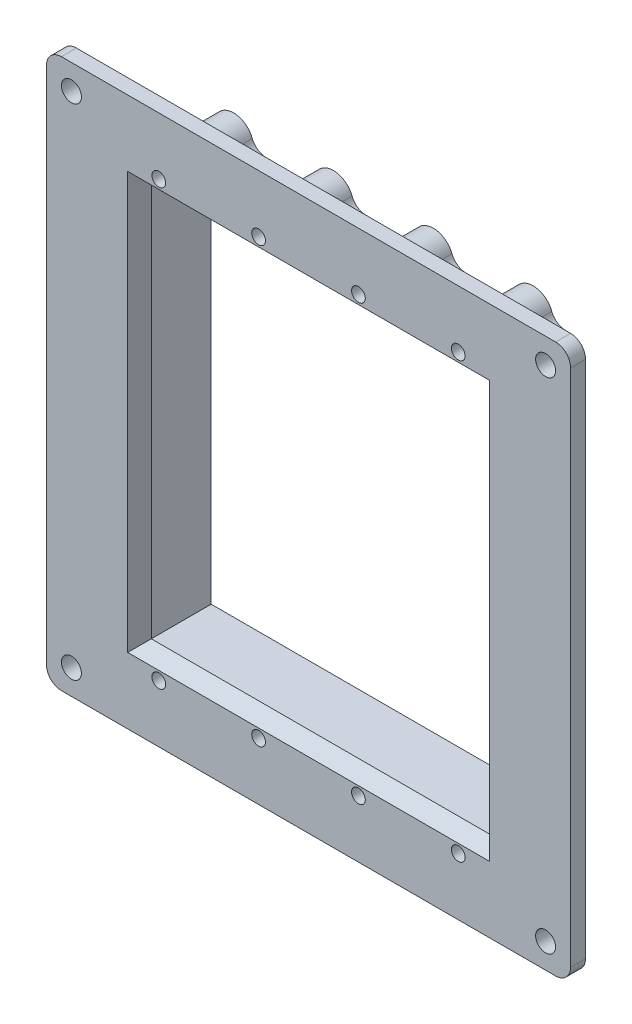
SolidWorks part; units mm, degrees
ref_plane "Front Plane" through (0, 0, 0) normal (0, 0, 1) x (1, 0, 0)
ref_plane "Top Plane" through (0, 0, 0) normal (0, 1, 0) x (1, 0, 0)
ref_plane "Right Plane" through (0, 0, 0) normal (1, 0, 0) x (0, 0, -1)
sketch "Sketch1" plane through (0, 0, 0) normal (0, 0, 1) x (1, 0, 0)
  line L0 (0, 43) -> (0, 43.5) construction
  line L1 (-52.5, 55) -> (52.5, 55)
  line L2 (-52.5, 55) -> (-52.5, -55)
  line L3 (-52.5, -55) -> (52.5, -55)
  line L4 (52.5, 55) -> (52.5, -55)
  line L5 (-52.5, 55) -> (52.5, -55) construction
  line L6 (-52.5, -55) -> (52.5, 55) construction
  line L7 (-37.5, 43) -> (37.5, 43)
  line L8 (-37.5, 43) -> (-37.5, -43)
  line L9 (-37.5, -43) -> (37.5, -43)
  line L10 (37.5, 43) -> (37.5, -43)
  line L11 (-37.5, 43) -> (37.5, -43) construction
  line L12 (-37.5, -43) -> (37.5, 43) construction
  line L13 (-34.5, 40) -> (34.5, 40)
  line L14 (-34.5, 40) -> (-34.5, -40)
  line L15 (-34.5, -40) -> (34.5, -40)
  line L16 (34.5, 40) -> (34.5, -40)
  line L17 (-34.5, 40) -> (34.5, -40) construction
  line L18 (-34.5, -40) -> (34.5, 40) construction
  line L19 (-47.5, -50) -> (47.5, -50) construction
  line L20 (-47.5, -50) -> (-47.5, 50) construction
  line L21 (-47.5, 50) -> (47.5, 50) construction
  line L22 (47.5, -50) -> (47.5, 50) construction
  line L23 (-47.5, -50) -> (47.5, 50) construction
  line L24 (-47.5, 50) -> (47.5, -50) construction
  line L25 (0, 43.5) -> (37.5, 43.5) construction
  line L26 (37.5, 43.5) -> (37.5, 43) construction
  line L27 (30, 43.5) -> (30, 43) construction
  line L28 (34, 43.5) -> (34, 43)
  line L29 (26, 43.5) -> (26, 43)
  line L30 (14, 43.5) -> (14, 43)
  line L31 (6, 43.5) -> (6, 43)
  line L32 (0, 0) -> (0, 55) construction
  line L33 (0, 0) -> (-52.5, 0) construction
  line L34 (-34, 43.5) -> (-34, 43)
  line L35 (-26, 43.5) -> (-26, 43)
  line L36 (-6, 43.5) -> (-6, 43)
  line L37 (-14, 43.5) -> (-14, 43)
  line L38 (30, -43.5) -> (30, -43) construction
  line L39 (37.5, -43.5) -> (37.5, -43) construction
  line L41 (0, -43) -> (0, -43.5) construction
  line L42 (-14, -43.5) -> (-14, -43)
  line L43 (-6, -43.5) -> (-6, -43)
  line L44 (-26, -43.5) -> (-26, -43)
  line L45 (-34, -43.5) -> (-34, -43)
  line L46 (6, -43.5) -> (6, -43)
  line L47 (14, -43.5) -> (14, -43)
  line L48 (26, -43.5) -> (26, -43)
  line L49 (34, -43.5) -> (34, -43)
  circle A0 centre (-47.5, 50) radius 2
  circle A1 centre (47.5, 50) radius 2
  circle A2 centre (-47.5, -50) radius 2
  circle A3 centre (47.5, -50) radius 2
  circle A5 centre (30, 43.5) radius 1.375
  circle A6 centre (10, 43.5) radius 1.375
  arc A7 (34, 43.5) -> (26, 43.5) centre (30, 43.5) ccw
  arc A9 (14, 43.5) -> (6, 43.5) centre (10, 43.5) ccw
  arc A10 (-34, 43.5) -> (-26, 43.5) centre (-30, 43.5) cw
  circle A11 centre (-30, 43.5) radius 1.375
  circle A12 centre (-10, 43.5) radius 1.375
  arc A13 (-14, 43.5) -> (-6, 43.5) centre (-10, 43.5) cw
  arc A14 (-14, -43.5) -> (-6, -43.5) centre (-10, -43.5) ccw
  circle A15 centre (-10, -43.5) radius 1.375
  circle A16 centre (-30, -43.5) radius 1.375
  arc A17 (-34, -43.5) -> (-26, -43.5) centre (-30, -43.5) ccw
  arc A18 (14, -43.5) -> (6, -43.5) centre (10, -43.5) cw
  arc A19 (34, -43.5) -> (26, -43.5) centre (30, -43.5) cw
  circle A20 centre (10, -43.5) radius 1.375
  circle A21 centre (30, -43.5) radius 1.375
  point P0 (0, 0)
  point P6 (0, 0)
  point P11 (0, 0)
  point P16 (0, 0)
  point P33 (50, 19.5)
  point P86 (50, -19.5)
  dimension "D7" = 4
  dimension "D13" = 2.75
  dimension "D14" = 4
  dimension "D1" = 3
  dimension "D2" = 105
  dimension "D3" = 75
  dimension "D4" = 3
  dimension "D5" = 80
  dimension "D6" = 110
  dimension "D8" = 5
  dimension "D9" = 5
  dimension "D10" = 0.5
  dimension "D11" = 10
  dimension "D12" = 20
  dimension "D15" = 2
extrude "Boss-Extrude1" add sketch "Sketch1" along normal blind 3 contours L4 L1 L2 L3 A3 A2 A1 A0 L49 A19 L48 L9 L47 A18 L46 L43 A14 L42 L44 A17 L45 L8 L7 L34 A10 L35 L37 A13 L36 L31 A9 L30 L29 A7 L28 L10 | L10 L7 L8 L9 L13 L16 L15 L14 | L28 A7 L29 L7 A5 | L30 A9 L31 L7 A6 | A13 L37 L7 L36 A12 | A10 L34 L7 L35 A11 | L45 A17 L44 L9 A16 | L42 A14 L43 L9 A15 | A18 L47 L9 L46 A20 | A19 L49 L9 L48 A21 region at (0, 53.4793, 0) region at (-35.75, 41.8589, 0) region at (-30, 45.1224, 0) region at (-30, -45.1224, 0) region at (-10, 45.1224, 0) region at (-10, -45.1224, 0) region at (10, 45.1224, 0) region at (10, -45.1224, 0) region at (30, 45.1224, 0) region at (30, -45.1224, 0)
extrude "Boss-Extrude2" add sketch "Sketch1<3>" against normal blind 15 from surface contours L10 L7 L8 L9 L13 L16 L15 L14 | L28 A7 L29 L7 A5 | L30 A9 L31 L7 A6 | A13 L37 L7 L36 A12 | A10 L34 L7 L35 A11 | L45 A17 L44 L9 A16 | L42 A14 L43 L9 A15 | A18 L47 L9 L46 A20 | A19 L49 L9 L48 A21 region at (-35.75, 41.8589, 0) region at (-30, 45.1224, 0) region at (-30, -45.1224, 0) region at (-10, 45.1224, 0) region at (-10, -45.1224, 0) region at (10, 45.1224, 0) region at (10, -45.1224, 0) region at (30, 45.1224, 0) region at (30, -45.1224, 0) starting at face at (-8.625, 43.5, 3)
sketch "Sketch1<3>" plane through (0, 0, 0) normal (0, 0, 1) x (1, 0, 0) same geometry as "Sketch1"
fillet "Fillet1" radius 3 20 edges at (34, -43, -6) (34, 43, -6) (26, 43, -6) (14, 43, -6) (6, 43, -6) (-6, 43, -6) (-14, 43, -6) (-26, 43, -6) (-34, 43, -6) (-34, -43, -6) (-26, -43, -6) (-14, -43, -6) (-6, -43, -6) (6, -43, -6) (14, -43, -6) (26, -43, -6) (-52.5, -55, 1.5) (-52.5, 55, 1.5) (52.5, 55, 1.5) (52.5, -55, 1.5)
chamfer "Chamfer1" distance 3 angle 30 40 edges at (34.5, 0, 3) (0, -40, 3) (-34.5, 0, 3) (0, 40, 3) (37.0192, -43, 0) (-37.0192, -43, 0) (-37.5, 0, 0) (37.0192, 43, 0) (-37.0192, 43, 0) (37.5, 0, 0) (25.1625, -43.5287, 0) (20, -43, 0) (14.8375, -43.5287, 0) (10, -47.5, 0) (5.1625, -43.5287, 0) (0, -43, 0) (-5.1625, -43.5287, 0) (-10, -47.5, 0) (-14.8375, -43.5287, 0) (-20, -43, 0) (-25.1625, -43.5287, 0) (-30, -47.5, 0) (-34.8375, -43.5287, 0) (-34.8375, 43.5287, 0) (-30, 47.5, 0) (-25.1625, 43.5287, 0) (-20, 43, 0) (-14.8375, 43.5287, 0) (-10, 47.5, 0) (-5.1625, 43.5287, 0) (0, 43, 0) (5.1625, 43.5287, 0) (10, 47.5, 0) (14.8375, 43.5287, 0) (20, 43, 0) (25.1625, 43.5287, 0) (30, 47.5, 0) (34.8375, 43.5287, 0) (34.8375, -43.5287, 0) (30, -47.5, 0) first distance on face at (34.5, 0, -4.5) first distance on face at (0, -40, -4.5) first distance on face at (-34.5, 0, -4.5) first distance on face at (0, 40, -4.5) first distance on face at (37.0192, -43, -6) first distance on face at (-37.0192, -43, -6) first distance on face at (-37.5, 0, -6) first distance on face at (37.0192, 43, -6) first distance on face at (-37.0192, 43, -6) first distance on face at (37.5, 0, -6) first distance on face at (25.0126, -43.7465, -6) first distance on face at (20, -43, -6) first distance on face at (14.9874, -43.7465, -6) first distance on face at (10, -46.2143, -6) first distance on face at (5.0126, -43.7465, -6) first distance on face at (0, -43, -6) first distance on face at (-5.0126, -43.7465, -6) first distance on face at (-10, -46.2143, -6) first distance on face at (-14.9874, -43.7465, -6) first distance on face at (-20, -43, -6) first distance on face at (-25.0126, -43.7465, -6) first distance on face at (-30, -46.2143, -6) first distance on face at (-34.9874, -43.7465, -6) first distance on face at (-34.9874, 43.7465, -6) first distance on face at (-30, 46.2143, -6) first distance on face at (-25.0126, 43.7465, -6) first distance on face at (-20, 43, -6) first distance on face at (-14.9874, 43.7465, -6) first distance on face at (-10, 46.2143, -6) first distance on face at (-5.0126, 43.7465, -6) first distance on face at (0, 43, -6) first distance on face at (5.0126, 43.7465, -6) first distance on face at (10, 46.2143, -6) first distance on face at (14.9874, 43.7465, -6) first distance on face at (20, 43, -6) first distance on face at (25.0126, 43.7465, -6) first distance on face at (30, 46.2143, -6) first distance on face at (34.9874, 43.7465, -6) first distance on face at (34.9874, -43.7465, -6) first distance on face at (30, -46.2143, -6)
equation "\"D4@Sketch1\"=\"D1@Sketch1\""
equation "\"D6@Sketch1\"=\"D5@Sketch1\"+30"
equation "\"D2@Sketch1\"=\"D3@Sketch1\"+30"
equation "\"D9@Sketch1\"=\"D8@Sketch1\""
equation "\"D3@Sketch1\"=(\"D11@Sketch1\"+\"D12@Sketch1\")*2+15"
equation "\"D12@Sketch1\"=\"D11@Sketch1\"*2"
